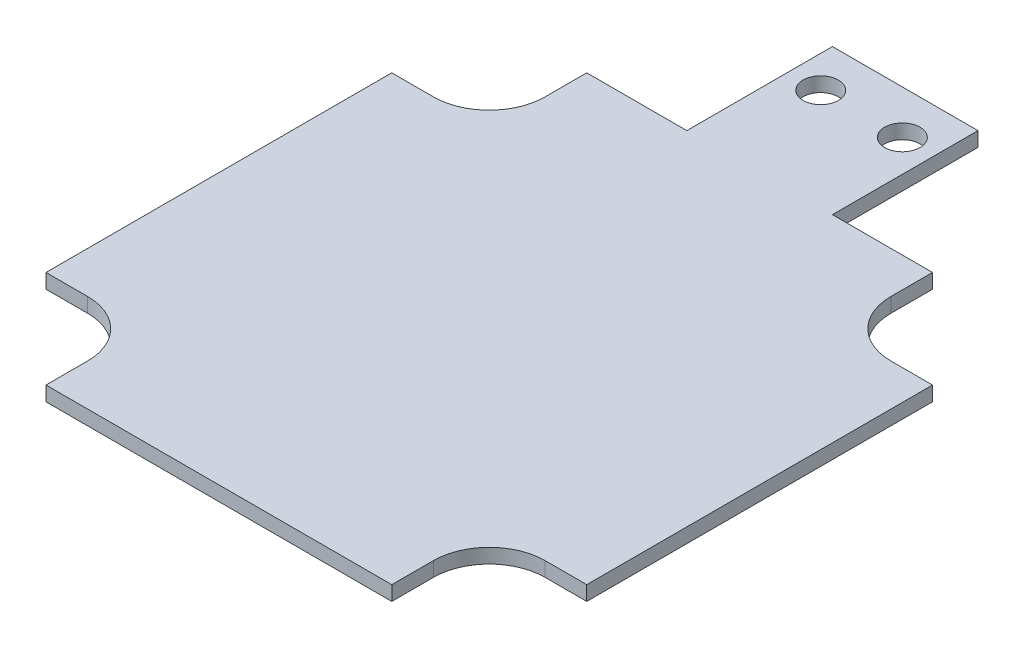
SolidWorks part; units mm, degrees
ref_plane "Front" through (0, 0, 0) normal (0, 0, 1) x (1, 0, 0)
ref_plane "Top" through (0, 0, 0) normal (0, 1, 0) x (1, 0, 0)
ref_plane "Right" through (0, 0, 0) normal (1, 0, 0) x (0, 0, -1)
sketch "Sketch1" plane through (0, 0, 0) normal (0, 1, 0) x (1, 0, 0)
  line L0 (0, 0) -> (0, 44.8031) construction
  line L1 (26, -26) -> (-26, -26)
  line L2 (26, -26) -> (26, 26)
  line L3 (26, 26) -> (7, 26)
  line L4 (-26, -26) -> (-26, 26)
  line L5 (26, -26) -> (-26, 26) construction
  line L6 (26, 26) -> (-26, -26) construction
  line L8 (-7, 26) -> (-7, 40)
  line L9 (-7, 40) -> (7, 40)
  line L10 (7, 26) -> (7, 40)
  line L11 (-7, 26) -> (-26, 26)
  point P0 (0, 0)
  dimension "D1" = 52
  dimension "D2" = 52
  dimension "D3" = 14
  dimension "D4" = 14
extrude "Boss-Extrude1" add sketch "Sketch1" along normal blind 1.4
sketch "Sketch2" plane through (0, 0, 0) normal (0, 1, 0) x (1, 0, 0)
  line L0 (16.5892, 0) -> (0, 0) construction
  line L1 (0, 0) -> (0, 17.8777) construction
  line L2 (-26, 26) -> (-26, -26) construction
  line L3 (26, 26) -> (7, 26) construction
  circle A0 centre (-22, 22) radius 1.25
  circle A1 centre (22, 22) radius 1.25
  circle A2 centre (22, -22) radius 1.25
  circle A3 centre (-22, -22) radius 1.25
  dimension "D2" = 4
  dimension "D3" = 2.5
  dimension "D4" = 4
extrude "Cut-Extrude2" cut sketch "Sketch2" along normal through all
sketch "Sketch5" plane through (0, 1.4, 0) normal (0, 1, 0) x (1, 0, 0)
  line L0 (-26, 26) -> (-16.625, 26)
  line L1 (-26, 26) -> (-26, 16.625)
  line L2 (0, 0) -> (0, 34.3484) construction
  line L3 (0, 0) -> (38.2278, 0) construction
  line L4 (22, 16.625) -> (26, 16.625)
  line L5 (16.625, 26) -> (16.625, 22)
  line L6 (26, 26) -> (26, 16.625)
  line L7 (26, 26) -> (16.625, 26)
  line L8 (-22, -16.625) -> (-26, -16.625)
  line L9 (-16.625, -26) -> (-16.625, -22)
  line L10 (26, -26) -> (16.625, -26)
  line L11 (-26, 26) -> (-26, -26) construction
  line L12 (-16.625, 26) -> (-16.625, 22)
  line L13 (-22, 16.625) -> (-26, 16.625)
  line L14 (26, 26) -> (7, 26) construction
  line L15 (26, -26) -> (26, -16.625)
  line L16 (16.625, -26) -> (16.625, -22)
  line L17 (22, -16.625) -> (26, -16.625)
  line L18 (-26, -26) -> (-26, -16.625)
  line L19 (-26, -26) -> (-16.625, -26)
  arc A0 (-22, 16.625) -> (-16.625, 22) centre (-22, 22) ccw
  circle A1 centre (-22, 22) radius 1.25 construction
  arc A2 (22, 16.625) -> (16.625, 22) centre (22, 22) cw
  arc A3 (22, -16.625) -> (16.625, -22) centre (22, -22) ccw
  arc A4 (-22, -16.625) -> (-16.625, -22) centre (-22, -22) cw
  dimension "D1" = 10.75
extrude "Cut-Extrude3" cut sketch "Sketch5" against normal through all
ref_axis "Axis1" through (0, -50, 0) along (0, 1, 0)
ref_plane "Plane1" through (0, 0, 0) normal (0.7071, 0, 0.7071) x (0.7071, 0, -0.7071)
ref_plane "Plane2" through (0, 0, 0) normal (-0.7071, 0, 0.7071) x (0.7071, 0, 0.7071)
sketch "Sketch6" plane through (0, 1.4, 0) normal (0, 1, 0) x (1, 0, 0)
  line L0 (7, 40) -> (-7, 40) construction
  line L1 (0, 40) -> (0, 0) construction
  circle A0 centre (3.925, 35.8) radius 1.7
  circle A1 centre (-3.925, 35.8) radius 1.7
  dimension "D3" = 3.4
  dimension "D1" = 4.2
  dimension "D2" = 7.85
extrude "Cut-Extrude4" cut sketch "Sketch6" against normal through all
